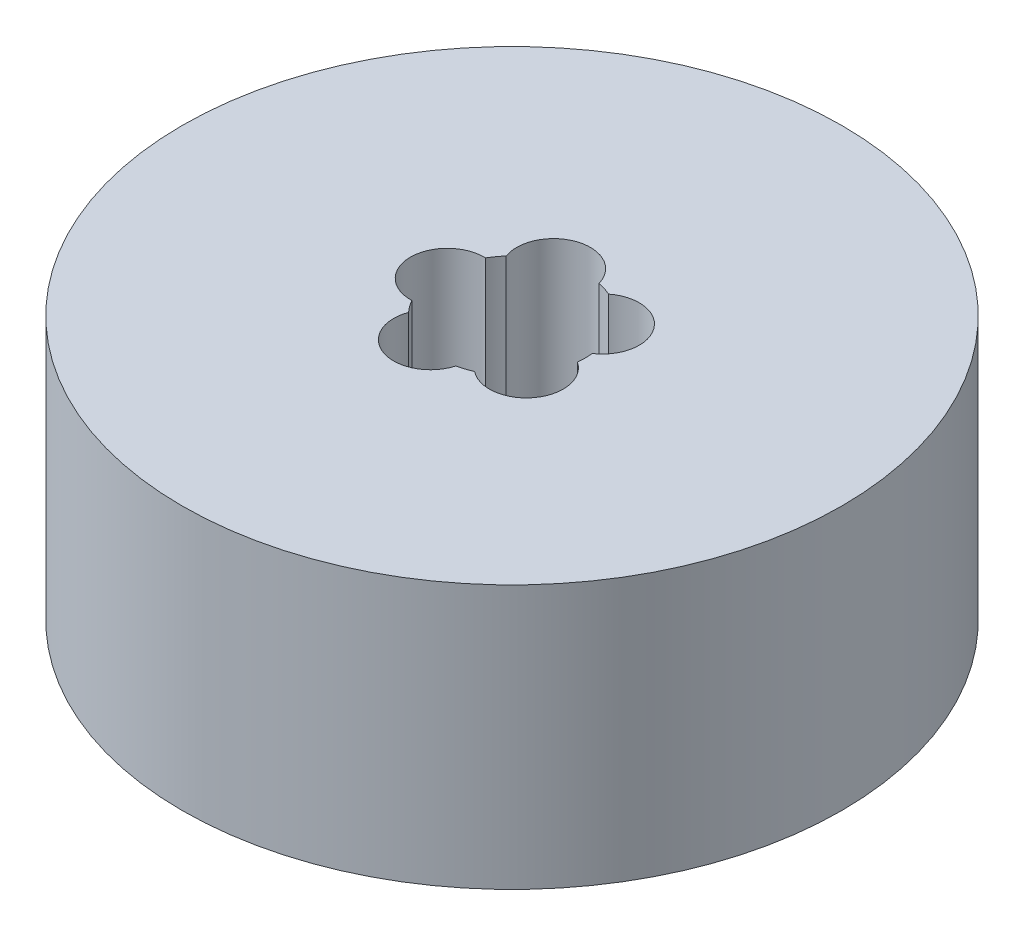
SolidWorks part; units mm, degrees
ref_plane "Front Plane" through (0, 0, 0) normal (0, 0, 1) x (1, 0, 0)
ref_plane "Top Plane" through (0, 0, 0) normal (0, 1, 0) x (1, 0, 0)
ref_plane "Right Plane" through (0, 0, 0) normal (1, 0, 0) x (0, 0, -1)
sketch "Sketch1" plane through (0, 0, 0) normal (0, 1, 0) x (1, 0, 0)
  circle A0 centre (0, 0) radius 22.5
  dimension "FLANGE_OD" = 45
extrude "Boss-Extrude1" add sketch "Sketch1" along normal blind 18
sketch "Sketch2" plane through (0, 0, 0) normal (0, 1, 0) x (1, 0, 0)
  circle A0 centre (0, 0) radius 5
  dimension "BORE_D" = 10
extrude "Cut-Extrude1" cut sketch "Sketch2" along normal through all
sketch "Sketch3" plane through (0, 18, 0) normal (0, 1, 0) x (1, 0, 0)
  circle A0 centre (0, 0) radius 4.4137 construction
  circle A1 centre (-4.4137, 0) radius 2.516
  dimension "BOLT_D" = 5.0321
  dimension "BOLT_PCD" = 8.8274
extrude "Cut-Extrude2" cut sketch "Sketch3" against normal blind 16.894
pattern_circular "CirPattern1" count 5 over 360 about axis through (0, 0, 0) along (0, 1, 0) of "Cut-Extrude2"
